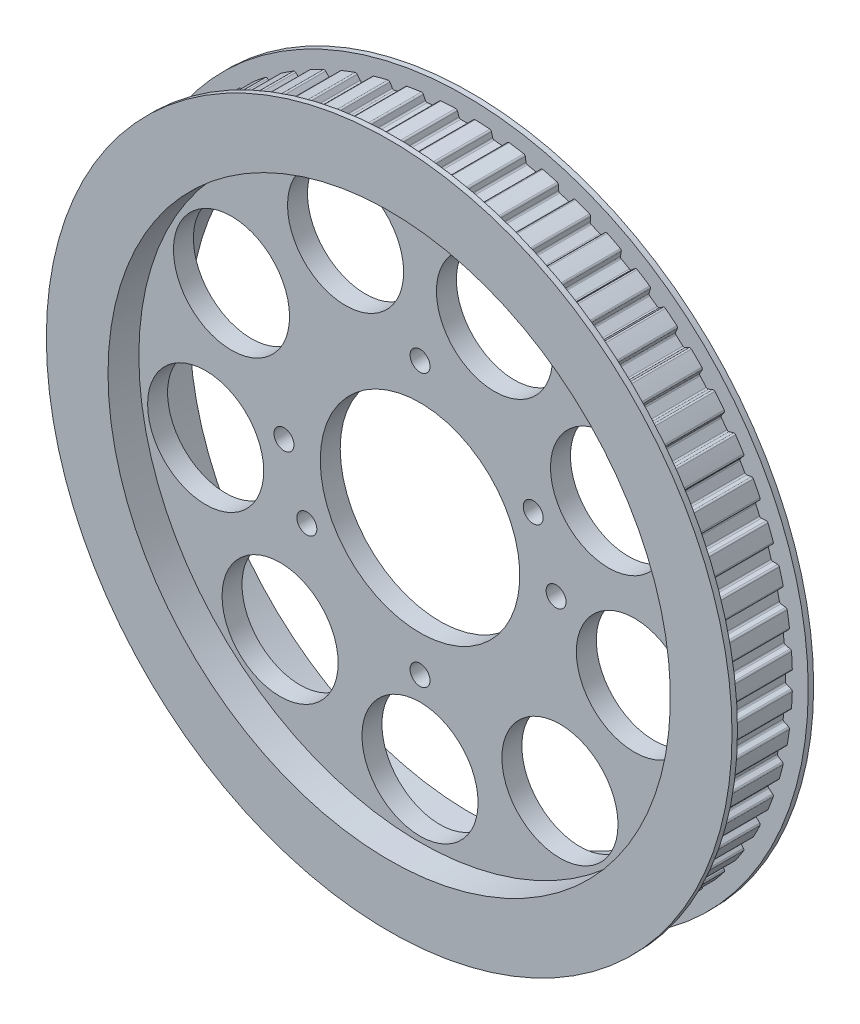
SolidWorks part; units mm, degrees
ref_plane "Front Plane" through (0, 0, 0) normal (0, 0, 1) x (1, 0, 0)
ref_plane "Top Plane" through (0, 0, 0) normal (0, 1, 0) x (1, 0, 0)
ref_plane "Right Plane" through (0, 0, 0) normal (1, 0, 0) x (0, 0, -1)
sketch "Sketch1" plane through (0, 0, 0) normal (0, 1, 0) x (1, 0, 0)
  line L0 (0, 41.5473) -> (0, -30.0211) construction
  line L1 (27.5, 2.75) -> (27.5, -2.75)
  line L2 (27.5, -2.75) -> (77.5, -2.75)
  line L3 (77.5, -2.75) -> (77.5, -11.25)
  line L4 (77.5, -11.25) -> (94.5, -11.25)
  line L5 (94.5, -11.25) -> (94.5, 11.25)
  line L6 (94.5, 11.25) -> (77.5, 11.25)
  line L7 (77.5, 11.25) -> (77.5, 2.75)
  line L8 (77.5, 2.75) -> (27.5, 2.75)
  line L9 (0, 0) -> (27.5, 0) construction
  line L10 (27.5, 0) -> (94.5, 0) construction
  dimension "D1" = 27.5
  dimension "D2" = 17
  dimension "D3" = 22.5
  dimension "D4" = 94.5
  dimension "D5" = 5.5
revolve "Revolve1" add sketch "Sketch1" angle 360 about L0
sketch "Sketch6" plane through (0, 0, 0) normal (0, 0, 1) x (1, 0, 0)
  line L0 (0, 0) -> (0, 89.1601) construction
  line L1 (-2.325, 90.1151) -> (-2.9401, 91.8051) construction
  line L2 (-2.325, 90.1151) -> (-1.6298, 88.2051) construction
  line L3 (-1.6298, 88.2051) -> (1.6298, 88.2051) construction
  line L4 (1.6298, 88.2051) -> (2.325, 90.1151) construction
  line L5 (2.325, 90.1151) -> (-2.325, 90.1151) construction
  line L6 (0, 88.2051) -> (0, 90.1151) construction
  line L7 (-2.9401, 91.8051) -> (2.9401, 91.8051) construction
  line L8 (2.9401, 91.8051) -> (2.325, 90.1151) construction
  line L9 (0, 90.1151) -> (0, 90.1451) construction
  line L10 (0, 90.1451) -> (0, 91.8522) construction
  line L11 (0, 0) -> (9.3198, 88.6717) construction
  line L12 (9.3198, 88.6717) -> (9.4227, 89.6513) construction
  line L13 (9.4227, 89.6513) -> (9.6012, 91.349) construction
  line L14 (0, 90.9986) -> (9.5119, 90.5001) construction
  circle A0 centre (0, 0) radius 94.5
  circle A1 centre (0, 0) radius 89.1601 construction
  circle A2 centre (-1.2727, 88.7151) radius 0.51 construction
  circle A3 centre (1.2727, 88.7151) radius 0.51 construction
  circle A4 centre (0, 0) radius 90.1451
  circle A5 centre (0, 0) radius 94.5 construction
  circle A6 centre (0, 0) radius 91.8522 construction
  dimension "D3" = 40
  dimension "D6" = 1.02
  dimension "D1" = 9.525
  dimension "D2" = 3.6
  dimension "D7" = 6
  dimension "D4" = 1.91
  dimension "D5" = 4.65
extrude "Cut-Extrude6" cut sketch "Sketch6" against normal offset from surface 1.5 and the other way offset from surface 1.5 up to face at (-77.5, 0, -11.25) other way up to face at (-94.5, 0, 11.25)
sketch "Sketch7" plane through (0, 0, 0) normal (0, 0, 1) x (1, 0, 0)
  line L0 (-1.6298, 88.2051) -> (-2.3359, 90.1451)
  line L1 (-2.3359, 90.1451) -> (2.3359, 90.1451)
  line L2 (2.3359, 90.1451) -> (1.6298, 88.2051)
  line L3 (1.6298, 88.2051) -> (-1.6298, 88.2051)
  line L4 (-2.325, 90.1151) -> (-1.6298, 88.2051) construction
  line L5 (1.6298, 88.2051) -> (2.325, 90.1151) construction
  line L6 (7.5991, 87.8923) -> (7.0996, 89.8954)
  line L7 (7.0996, 89.8954) -> (11.7458, 89.4071)
  line L8 (11.7458, 89.4071) -> (10.8408, 87.5515)
  line L9 (10.8408, 87.5515) -> (7.5991, 87.8923)
  line L10 (16.7447, 86.6165) -> (16.4573, 88.6609)
  line L11 (16.4573, 88.6609) -> (21.0271, 87.6895)
  line L12 (21.0271, 87.6895) -> (19.9331, 85.9387)
  line L13 (19.9331, 85.9387) -> (16.7447, 86.6165)
  line L14 (25.7068, 84.3917) -> (25.6348, 86.4549)
  line L15 (25.6348, 86.4549) -> (30.0779, 85.0112)
  line L16 (30.0779, 85.0112) -> (28.8069, 83.3844)
  line L17 (28.8069, 83.3844) -> (25.7068, 84.3917)
  line L18 (34.3873, 81.2423) -> (34.5313, 83.3017)
  line L19 (34.5313, 83.3017) -> (38.7993, 81.4015)
  line L20 (38.7993, 81.4015) -> (37.3652, 79.9165)
  line L21 (37.3652, 79.9165) -> (34.3873, 81.2423)
  line L22 (42.6911, 77.2028) -> (43.0496, 79.2359)
  line L23 (43.0496, 79.2359) -> (47.0955, 76.9)
  line L24 (47.0955, 76.9) -> (45.514, 75.5729)
  line L25 (45.514, 75.5729) -> (42.6911, 77.2028)
  line L26 (50.5271, 72.3174) -> (51.0962, 74.3019)
  line L27 (51.0962, 74.3019) -> (54.8757, 71.5559)
  line L28 (54.8757, 71.5559) -> (53.1642, 70.4014)
  line L29 (53.1642, 70.4014) -> (50.5271, 72.3174)
  line L30 (57.8095, 66.6397) -> (58.5829, 68.5539)
  line L31 (58.5829, 68.5539) -> (62.0548, 65.4278)
  line L32 (62.0548, 65.4278) -> (60.2319, 64.4586)
  line L33 (60.2319, 64.4586) -> (57.8095, 66.6397)
  line L34 (64.4586, 60.2319) -> (65.4278, 62.0548)
  line L35 (65.4278, 62.0548) -> (68.5539, 58.5829)
  line L36 (68.5539, 58.5829) -> (66.6397, 57.8095)
  line L37 (66.6397, 57.8095) -> (64.4586, 60.2319)
  line L38 (70.4014, 53.1642) -> (71.5559, 54.8757)
  line L39 (71.5559, 54.8757) -> (74.3019, 51.0962)
  line L40 (74.3019, 51.0962) -> (72.3174, 50.5271)
  line L41 (72.3174, 50.5271) -> (70.4014, 53.1642)
  line L42 (75.5729, 45.514) -> (76.9, 47.0955)
  line L43 (76.9, 47.0955) -> (79.2359, 43.0496)
  line L44 (79.2359, 43.0496) -> (77.2028, 42.6911)
  line L45 (77.2028, 42.6911) -> (75.5729, 45.514)
  line L46 (79.9165, 37.3652) -> (81.4015, 38.7993)
  line L47 (81.4015, 38.7993) -> (83.3017, 34.5313)
  line L48 (83.3017, 34.5313) -> (81.2423, 34.3873)
  line L49 (81.2423, 34.3873) -> (79.9165, 37.3652)
  line L50 (83.3844, 28.8069) -> (85.0112, 30.0779)
  line L51 (85.0112, 30.0779) -> (86.4549, 25.6348)
  line L52 (86.4549, 25.6348) -> (84.3917, 25.7068)
  line L53 (84.3917, 25.7068) -> (83.3844, 28.8069)
  line L54 (85.9387, 19.9331) -> (87.6895, 21.0271)
  line L55 (87.6895, 21.0271) -> (88.6609, 16.4573)
  line L56 (88.6609, 16.4573) -> (86.6165, 16.7447)
  line L57 (86.6165, 16.7447) -> (85.9387, 19.9331)
  line L58 (87.5515, 10.8408) -> (89.4071, 11.7458)
  line L59 (89.4071, 11.7458) -> (89.8954, 7.0996)
  line L60 (89.8954, 7.0996) -> (87.8923, 7.5991)
  line L61 (87.8923, 7.5991) -> (87.5515, 10.8408)
  line L62 (88.2051, 1.6298) -> (90.1451, 2.3359)
  line L63 (90.1451, 2.3359) -> (90.1451, -2.3359)
  line L64 (90.1451, -2.3359) -> (88.2051, -1.6298)
  line L65 (88.2051, -1.6298) -> (88.2051, 1.6298)
  line L66 (87.8923, -7.5991) -> (89.8954, -7.0996)
  line L67 (89.8954, -7.0996) -> (89.4071, -11.7458)
  line L68 (89.4071, -11.7458) -> (87.5515, -10.8408)
  line L69 (87.5515, -10.8408) -> (87.8923, -7.5991)
  line L70 (86.6165, -16.7447) -> (88.6609, -16.4573)
  line L71 (88.6609, -16.4573) -> (87.6895, -21.0271)
  line L72 (87.6895, -21.0271) -> (85.9387, -19.9331)
  line L73 (85.9387, -19.9331) -> (86.6165, -16.7447)
  line L74 (84.3917, -25.7068) -> (86.4549, -25.6348)
  line L75 (86.4549, -25.6348) -> (85.0112, -30.0779)
  line L76 (85.0112, -30.0779) -> (83.3844, -28.8069)
  line L77 (83.3844, -28.8069) -> (84.3917, -25.7068)
  line L78 (81.2423, -34.3873) -> (83.3017, -34.5313)
  line L79 (83.3017, -34.5313) -> (81.4015, -38.7993)
  line L80 (81.4015, -38.7993) -> (79.9165, -37.3652)
  line L81 (79.9165, -37.3652) -> (81.2423, -34.3873)
  line L82 (77.2028, -42.6911) -> (79.2359, -43.0496)
  line L83 (79.2359, -43.0496) -> (76.9, -47.0955)
  line L84 (76.9, -47.0955) -> (75.5729, -45.514)
  line L85 (75.5729, -45.514) -> (77.2028, -42.6911)
  line L86 (72.3174, -50.5271) -> (74.3019, -51.0962)
  line L87 (74.3019, -51.0962) -> (71.5559, -54.8757)
  line L88 (71.5559, -54.8757) -> (70.4014, -53.1642)
  line L89 (70.4014, -53.1642) -> (72.3174, -50.5271)
  line L90 (66.6397, -57.8095) -> (68.5539, -58.5829)
  line L91 (68.5539, -58.5829) -> (65.4278, -62.0548)
  line L92 (65.4278, -62.0548) -> (64.4586, -60.2319)
  line L93 (64.4586, -60.2319) -> (66.6397, -57.8095)
  line L94 (60.2319, -64.4586) -> (62.0548, -65.4278)
  line L95 (62.0548, -65.4278) -> (58.5829, -68.5539)
  line L96 (58.5829, -68.5539) -> (57.8095, -66.6397)
  line L97 (57.8095, -66.6397) -> (60.2319, -64.4586)
  line L98 (53.1642, -70.4014) -> (54.8757, -71.5559)
  line L99 (54.8757, -71.5559) -> (51.0962, -74.3019)
  line L100 (51.0962, -74.3019) -> (50.5271, -72.3174)
  line L101 (50.5271, -72.3174) -> (53.1642, -70.4014)
  line L102 (45.514, -75.5729) -> (47.0955, -76.9)
  line L103 (47.0955, -76.9) -> (43.0496, -79.2359)
  line L104 (43.0496, -79.2359) -> (42.6911, -77.2028)
  line L105 (42.6911, -77.2028) -> (45.514, -75.5729)
  line L106 (37.3652, -79.9165) -> (38.7993, -81.4015)
  line L107 (38.7993, -81.4015) -> (34.5313, -83.3017)
  line L108 (34.5313, -83.3017) -> (34.3873, -81.2423)
  line L109 (34.3873, -81.2423) -> (37.3652, -79.9165)
  line L110 (28.8069, -83.3844) -> (30.0779, -85.0112)
  line L111 (30.0779, -85.0112) -> (25.6348, -86.4549)
  line L112 (25.6348, -86.4549) -> (25.7068, -84.3917)
  line L113 (25.7068, -84.3917) -> (28.8069, -83.3844)
  line L114 (19.9331, -85.9387) -> (21.0271, -87.6895)
  line L115 (21.0271, -87.6895) -> (16.4573, -88.6609)
  line L116 (16.4573, -88.6609) -> (16.7447, -86.6165)
  line L117 (16.7447, -86.6165) -> (19.9331, -85.9387)
  line L118 (10.8408, -87.5515) -> (11.7458, -89.4071)
  line L119 (11.7458, -89.4071) -> (7.0996, -89.8954)
  line L120 (7.0996, -89.8954) -> (7.5991, -87.8923)
  line L121 (7.5991, -87.8923) -> (10.8408, -87.5515)
  line L122 (1.6298, -88.2051) -> (2.3359, -90.1451)
  line L123 (2.3359, -90.1451) -> (-2.3359, -90.1451)
  line L124 (-2.3359, -90.1451) -> (-1.6298, -88.2051)
  line L125 (-1.6298, -88.2051) -> (1.6298, -88.2051)
  line L126 (-7.5991, -87.8923) -> (-7.0996, -89.8954)
  line L127 (-7.0996, -89.8954) -> (-11.7458, -89.4071)
  line L128 (-11.7458, -89.4071) -> (-10.8408, -87.5515)
  line L129 (-10.8408, -87.5515) -> (-7.5991, -87.8923)
  line L130 (-16.7447, -86.6165) -> (-16.4573, -88.6609)
  line L131 (-16.4573, -88.6609) -> (-21.0271, -87.6895)
  line L132 (-21.0271, -87.6895) -> (-19.9331, -85.9387)
  line L133 (-19.9331, -85.9387) -> (-16.7447, -86.6165)
  line L134 (-25.7068, -84.3917) -> (-25.6348, -86.4549)
  line L135 (-25.6348, -86.4549) -> (-30.0779, -85.0112)
  line L136 (-30.0779, -85.0112) -> (-28.8069, -83.3844)
  line L137 (-28.8069, -83.3844) -> (-25.7068, -84.3917)
  line L138 (-34.3873, -81.2423) -> (-34.5313, -83.3017)
  line L139 (-34.5313, -83.3017) -> (-38.7993, -81.4015)
  line L140 (-38.7993, -81.4015) -> (-37.3652, -79.9165)
  line L141 (-37.3652, -79.9165) -> (-34.3873, -81.2423)
  line L142 (-42.6911, -77.2028) -> (-43.0496, -79.2359)
  line L143 (-43.0496, -79.2359) -> (-47.0955, -76.9)
  line L144 (-47.0955, -76.9) -> (-45.514, -75.5729)
  line L145 (-45.514, -75.5729) -> (-42.6911, -77.2028)
  line L146 (-50.5271, -72.3174) -> (-51.0962, -74.3019)
  line L147 (-51.0962, -74.3019) -> (-54.8757, -71.5559)
  line L148 (-54.8757, -71.5559) -> (-53.1642, -70.4014)
  line L149 (-53.1642, -70.4014) -> (-50.5271, -72.3174)
  line L150 (-57.8095, -66.6397) -> (-58.5829, -68.5539)
  line L151 (-58.5829, -68.5539) -> (-62.0548, -65.4278)
  line L152 (-62.0548, -65.4278) -> (-60.2319, -64.4586)
  line L153 (-60.2319, -64.4586) -> (-57.8095, -66.6397)
  line L154 (-64.4586, -60.2319) -> (-65.4278, -62.0548)
  line L155 (-65.4278, -62.0548) -> (-68.5539, -58.5829)
  line L156 (-68.5539, -58.5829) -> (-66.6397, -57.8095)
  line L157 (-66.6397, -57.8095) -> (-64.4586, -60.2319)
  line L158 (-70.4014, -53.1642) -> (-71.5559, -54.8757)
  line L159 (-71.5559, -54.8757) -> (-74.3019, -51.0962)
  line L160 (-74.3019, -51.0962) -> (-72.3174, -50.5271)
  line L161 (-72.3174, -50.5271) -> (-70.4014, -53.1642)
  line L162 (-75.5729, -45.514) -> (-76.9, -47.0955)
  line L163 (-76.9, -47.0955) -> (-79.2359, -43.0496)
  line L164 (-79.2359, -43.0496) -> (-77.2028, -42.6911)
  line L165 (-77.2028, -42.6911) -> (-75.5729, -45.514)
  line L166 (-79.9165, -37.3652) -> (-81.4015, -38.7993)
  line L167 (-81.4015, -38.7993) -> (-83.3017, -34.5313)
  line L168 (-83.3017, -34.5313) -> (-81.2423, -34.3873)
  line L169 (-81.2423, -34.3873) -> (-79.9165, -37.3652)
  line L170 (-83.3844, -28.8069) -> (-85.0112, -30.0779)
  line L171 (-85.0112, -30.0779) -> (-86.4549, -25.6348)
  line L172 (-86.4549, -25.6348) -> (-84.3917, -25.7068)
  line L173 (-84.3917, -25.7068) -> (-83.3844, -28.8069)
  line L174 (-85.9387, -19.9331) -> (-87.6895, -21.0271)
  line L175 (-87.6895, -21.0271) -> (-88.6609, -16.4573)
  line L176 (-88.6609, -16.4573) -> (-86.6165, -16.7447)
  line L177 (-86.6165, -16.7447) -> (-85.9387, -19.9331)
  line L178 (-87.5515, -10.8408) -> (-89.4071, -11.7458)
  line L179 (-89.4071, -11.7458) -> (-89.8954, -7.0996)
  line L180 (-89.8954, -7.0996) -> (-87.8923, -7.5991)
  line L181 (-87.8923, -7.5991) -> (-87.5515, -10.8408)
  line L182 (-88.2051, -1.6298) -> (-90.1451, -2.3359)
  line L183 (-90.1451, -2.3359) -> (-90.1451, 2.3359)
  line L184 (-90.1451, 2.3359) -> (-88.2051, 1.6298)
  line L185 (-88.2051, 1.6298) -> (-88.2051, -1.6298)
  line L186 (-87.8923, 7.5991) -> (-89.8954, 7.0996)
  line L187 (-89.8954, 7.0996) -> (-89.4071, 11.7458)
  line L188 (-89.4071, 11.7458) -> (-87.5515, 10.8408)
  line L189 (-87.5515, 10.8408) -> (-87.8923, 7.5991)
  line L190 (-86.6165, 16.7447) -> (-88.6609, 16.4573)
  line L191 (-88.6609, 16.4573) -> (-87.6895, 21.0271)
  line L192 (-87.6895, 21.0271) -> (-85.9387, 19.9331)
  line L193 (-85.9387, 19.9331) -> (-86.6165, 16.7447)
  line L194 (-84.3917, 25.7068) -> (-86.4549, 25.6348)
  line L195 (-86.4549, 25.6348) -> (-85.0112, 30.0779)
  line L196 (-85.0112, 30.0779) -> (-83.3844, 28.8069)
  line L197 (-83.3844, 28.8069) -> (-84.3917, 25.7068)
  line L198 (-81.2423, 34.3873) -> (-83.3017, 34.5313)
  line L199 (-83.3017, 34.5313) -> (-81.4015, 38.7993)
  line L200 (-81.4015, 38.7993) -> (-79.9165, 37.3652)
  line L201 (-79.9165, 37.3652) -> (-81.2423, 34.3873)
  line L202 (-77.2028, 42.6911) -> (-79.2359, 43.0496)
  line L203 (-79.2359, 43.0496) -> (-76.9, 47.0955)
  line L204 (-76.9, 47.0955) -> (-75.5729, 45.514)
  line L205 (-75.5729, 45.514) -> (-77.2028, 42.6911)
  line L206 (-72.3174, 50.5271) -> (-74.3019, 51.0962)
  line L207 (-74.3019, 51.0962) -> (-71.5559, 54.8757)
  line L208 (-71.5559, 54.8757) -> (-70.4014, 53.1642)
  line L209 (-70.4014, 53.1642) -> (-72.3174, 50.5271)
  line L210 (-66.6397, 57.8095) -> (-68.5539, 58.5829)
  line L211 (-68.5539, 58.5829) -> (-65.4278, 62.0548)
  line L212 (-65.4278, 62.0548) -> (-64.4586, 60.2319)
  line L213 (-64.4586, 60.2319) -> (-66.6397, 57.8095)
  line L214 (-60.2319, 64.4586) -> (-62.0548, 65.4278)
  line L215 (-62.0548, 65.4278) -> (-58.5829, 68.5539)
  line L216 (-58.5829, 68.5539) -> (-57.8095, 66.6397)
  line L217 (-57.8095, 66.6397) -> (-60.2319, 64.4586)
  line L218 (-53.1642, 70.4014) -> (-54.8757, 71.5559)
  line L219 (-54.8757, 71.5559) -> (-51.0962, 74.3019)
  line L220 (-51.0962, 74.3019) -> (-50.5271, 72.3174)
  line L221 (-50.5271, 72.3174) -> (-53.1642, 70.4014)
  line L222 (-45.514, 75.5729) -> (-47.0955, 76.9)
  line L223 (-47.0955, 76.9) -> (-43.0496, 79.2359)
  line L224 (-43.0496, 79.2359) -> (-42.6911, 77.2028)
  line L225 (-42.6911, 77.2028) -> (-45.514, 75.5729)
  line L226 (-37.3652, 79.9165) -> (-38.7993, 81.4015)
  line L227 (-38.7993, 81.4015) -> (-34.5313, 83.3017)
  line L228 (-34.5313, 83.3017) -> (-34.3873, 81.2423)
  line L229 (-34.3873, 81.2423) -> (-37.3652, 79.9165)
  line L230 (-28.8069, 83.3844) -> (-30.0779, 85.0112)
  line L231 (-30.0779, 85.0112) -> (-25.6348, 86.4549)
  line L232 (-25.6348, 86.4549) -> (-25.7068, 84.3917)
  line L233 (-25.7068, 84.3917) -> (-28.8069, 83.3844)
  line L234 (-19.9331, 85.9387) -> (-21.0271, 87.6895)
  line L235 (-21.0271, 87.6895) -> (-16.4573, 88.6609)
  line L236 (-16.4573, 88.6609) -> (-16.7447, 86.6165)
  line L237 (-16.7447, 86.6165) -> (-19.9331, 85.9387)
  line L238 (-10.8408, 87.5515) -> (-11.7458, 89.4071)
  line L239 (-11.7458, 89.4071) -> (-7.0996, 89.8954)
  line L240 (-7.0996, 89.8954) -> (-7.5991, 87.8923)
  line L241 (-7.5991, 87.8923) -> (-10.8408, 87.5515)
  circle A0 centre (0, 0) radius 90.1451 construction
  point P251 (0, 0)
  dimension "D1" = 60
extrude "Cut-Extrude7" cut sketch "Sketch7" against normal up to surface (9.75 mm away) and the other way up to surface (9.75 mm away) up to face at (94.5, 0, -9.75) other way up to face at (-90.1451, 0, 9.75)
fillet "Fillet1" radius 0.51 240 edges at (88.2051, -1.6298, 0) (88.2051, 1.6298, 0) (90.1151, 2.325, 0) (89.8645, 7.1073, 0) (87.8923, 7.5991, 0) (87.5515, 10.8408, 0) (89.3784, 11.7319, 0) (88.6293, 16.4618, 0) (86.6165, 16.7447, 0) (85.9387, 19.9331, 0) (87.6625, 21.0102, 0) (86.423, 25.6359, 0) (84.3917, 25.7068, 0) (83.3844, 28.8069, 0) (84.9861, 30.0583, 0) (83.2699, 34.5291, 0) (81.2423, 34.3873, 0) (79.9165, 37.3652, 0) (81.3786, 38.7771, 0) (79.2045, 43.044, 0) (77.2028, 42.6911, 0) (75.5729, 45.514, 0) (76.8795, 47.0711, 0) (74.2712, 51.0874, 0) (72.3174, 50.5271, 0) (70.4014, 53.1642, 0) (71.538, 54.8493, 0) (68.5243, 58.571, 0) (66.6397, 57.8095, 0) (64.4586, 60.2319, 0) (65.4128, 62.0266, 0) (62.0266, 65.4128, 0) (60.2319, 64.4586, 0) (57.8095, 66.6397, 0) (58.571, 68.5243, 0) (54.8493, 71.538, 0) (53.1642, 70.4014, 0) (50.5271, 72.3174, 0) (51.0874, 74.2712, 0) (47.0711, 76.8795, 0) (45.514, 75.5729, 0) (42.6911, 77.2028, 0) (43.044, 79.2045, 0) (38.7771, 81.3786, 0) (37.3652, 79.9165, 0) (34.3873, 81.2423, 0) (34.5291, 83.2699, 0) (30.0583, 84.9861, 0) (28.8069, 83.3844, 0) (25.7068, 84.3917, 0) (25.6359, 86.423, 0) (21.0102, 87.6625, 0) (19.9331, 85.9387, 0) (16.7447, 86.6165, 0) (16.4618, 88.6293, 0) (11.7319, 89.3784, 0) (10.8408, 87.5515, 0) (7.5991, 87.8923, 0) (7.1073, 89.8645, 0) (2.325, 90.1151, 0) (1.6298, 88.2051, 0) (-1.6298, 88.2051, 0) (-7.1073, 89.8645, 0) (-7.5991, 87.8923, 0) (-10.8408, 87.5515, 0) (-11.7319, 89.3784, 0) (-16.4618, 88.6293, 0) (-16.7447, 86.6165, 0) (-19.9331, 85.9387, 0) (-21.0102, 87.6625, 0) (-25.6359, 86.423, 0) (-25.7068, 84.3917, 0) (-28.8069, 83.3844, 0) (-30.0583, 84.9861, 0) (-34.5291, 83.2699, 0) (-34.3873, 81.2423, 0) (-37.3652, 79.9165, 0) (-38.7771, 81.3786, 0) (-43.044, 79.2045, 0) (-42.6911, 77.2028, 0) (-45.514, 75.5729, 0) (-47.0711, 76.8795, 0) (-51.0874, 74.2712, 0) (-50.5271, 72.3174, 0) (-53.1642, 70.4014, 0) (-54.8493, 71.538, 0) (-58.571, 68.5243, 0) (-57.8095, 66.6397, 0) (-60.2319, 64.4586, 0) (-62.0266, 65.4128, 0) (-65.4128, 62.0266, 0) (-64.4586, 60.2319, 0) (-66.6397, 57.8095, 0) (-68.5243, 58.571, 0) (-71.538, 54.8493, 0) (-70.4014, 53.1642, 0) (-72.3174, 50.5271, 0) (-74.2712, 51.0874, 0) (-76.8795, 47.0711, 0) (-75.5729, 45.514, 0) (-77.2028, 42.6911, 0) (-79.2045, 43.044, 0) (-81.3786, 38.7771, 0) (-79.9165, 37.3652, 0) (-81.2423, 34.3873, 0) (-83.2699, 34.5291, 0) (-84.9861, 30.0583, 0) (-83.3844, 28.8069, 0) (-84.3917, 25.7068, 0) (-86.423, 25.6359, 0) (-87.6625, 21.0102, 0) (-85.9387, 19.9331, 0) (-86.6165, 16.7447, 0) (-88.6293, 16.4618, 0) (-89.3784, 11.7319, 0) (-87.5515, 10.8408, 0) (-87.8923, 7.5991, 0) (-89.8645, 7.1073, 0) (-90.1151, 2.325, 0) (-88.2051, 1.6298, 0) (-88.2051, -1.6298, 0) (-90.1151, -2.325, 0) (-89.8645, -7.1073, 0) (-87.8923, -7.5991, 0) (-87.5515, -10.8408, 0) (-89.3784, -11.7319, 0) (-88.6293, -16.4618, 0) (-86.6165, -16.7447, 0) (-85.9387, -19.9331, 0) (-87.6625, -21.0102, 0) (-86.423, -25.6359, 0) (-84.3917, -25.7068, 0) (-83.3844, -28.8069, 0) (-84.9861, -30.0583, 0) (-83.2699, -34.5291, 0) (-81.2423, -34.3873, 0) (-79.9165, -37.3652, 0) (-81.3786, -38.7771, 0) (-79.2045, -43.044, 0) (-77.2028, -42.6911, 0) (-75.5729, -45.514, 0) (-76.8795, -47.0711, 0) (-74.2712, -51.0874, 0) (-72.3174, -50.5271, 0) (-70.4014, -53.1642, 0) (-71.538, -54.8493, 0) (-68.5243, -58.571, 0) (-66.6397, -57.8095, 0) (-64.4586, -60.2319, 0) (-65.4128, -62.0266, 0) (-62.0266, -65.4128, 0) (-60.2319, -64.4586, 0) (-57.8095, -66.6397, 0) (-58.571, -68.5243, 0) (-54.8493, -71.538, 0) (-53.1642, -70.4014, 0) (-50.5271, -72.3174, 0) (-51.0874, -74.2712, 0) (-47.0711, -76.8795, 0) (-45.514, -75.5729, 0) (-42.6911, -77.2028, 0) (-43.044, -79.2045, 0) (-38.7771, -81.3786, 0) (-37.3652, -79.9165, 0) (-34.3873, -81.2423, 0) (-34.5291, -83.2699, 0) (-30.0583, -84.9861, 0) (-28.8069, -83.3844, 0) (-25.7068, -84.3917, 0) (-25.6359, -86.423, 0) (-21.0102, -87.6625, 0) (-19.9331, -85.9387, 0) (-16.7447, -86.6165, 0) (-16.4618, -88.6293, 0) (-11.7319, -89.3784, 0) (-10.8408, -87.5515, 0) (-7.5991, -87.8923, 0) (-7.1073, -89.8645, 0) (-2.325, -90.1151, 0) (-1.6298, -88.2051, 0) (1.6298, -88.2051, 0) (2.325, -90.1151, 0) (7.1073, -89.8645, 0) (7.5991, -87.8923, 0) (10.8408, -87.5515, 0) (11.7319, -89.3784, 0) (16.4618, -88.6293, 0) (16.7447, -86.6165, 0) (19.9331, -85.9387, 0) (21.0102, -87.6625, 0) (25.6359, -86.423, 0) (25.7068, -84.3917, 0) (28.8069, -83.3844, 0) (30.0583, -84.9861, 0) (34.5291, -83.2699, 0) (34.3873, -81.2423, 0) (37.3652, -79.9165, 0) (38.7771, -81.3786, 0) (43.044, -79.2045, 0) (42.6911, -77.2028, 0) (45.514, -75.5729, 0) (47.0711, -76.8795, 0) (51.0874, -74.2712, 0) (50.5271, -72.3174, 0) (53.1642, -70.4014, 0) (54.8493, -71.538, 0) (58.571, -68.5243, 0) (57.8095, -66.6397, 0) (60.2319, -64.4586, 0) (62.0266, -65.4128, 0) (65.4128, -62.0266, 0) (64.4586, -60.2319, 0) (66.6397, -57.8095, 0) (68.5243, -58.571, 0) (71.538, -54.8493, 0) (70.4014, -53.1642, 0) (72.3174, -50.5271, 0) (74.2712, -51.0874, 0) (76.8795, -47.0711, 0) (75.5729, -45.514, 0) (77.2028, -42.6911, 0) (79.2045, -43.044, 0) (81.3786, -38.7771, 0) (79.9165, -37.3652, 0) (81.2423, -34.3873, 0) (83.2699, -34.5291, 0) (84.9861, -30.0583, 0) (83.3844, -28.8069, 0) (84.3917, -25.7068, 0) (86.423, -25.6359, 0) (87.6625, -21.0102, 0) (85.9387, -19.9331, 0) (86.6165, -16.7447, 0) (88.6293, -16.4618, 0) (89.3784, -11.7319, 0) (87.5515, -10.8408, 0) (87.8923, -7.5991, 0) (89.8645, -7.1073, 0) (90.1151, -2.325, 0) (-2.325, 90.1151, 0)
sketch "Sketch3" plane through (0, 0, 0) normal (0, 0, 1) x (1, 0, 0)
  line L0 (0, 0) -> (0, 77.5) construction
  line L1 (0, 0) -> (9.4056, 25.8415) construction
  line L2 (15.0489, 41.3465) -> (20.5212, 56.3816) construction
  line L3 (20.5212, 56.3816) -> (25.9935, 71.4166) construction
  line L4 (25.9935, 71.4166) -> (26.5066, 72.8262) construction
  line L5 (9.4056, 25.8415) -> (15.0489, 41.3465) construction
  line L6 (-20.5212, 56.3816) -> (20.5212, 56.3816) construction
  circle A0 centre (20.5212, 56.3816) radius 16
  circle A1 centre (0, 0) radius 77.5 construction
  circle A2 centre (0, 0) radius 27.5 construction
  circle A3 centre (51.9615, 30) radius 16
  circle A4 centre (59.0885, -10.4189) radius 16
  circle A5 centre (38.5673, -45.9627) radius 16
  circle A6 centre (0, -60) radius 16
  circle A7 centre (-38.5673, -45.9627) radius 16
  circle A8 centre (-59.0885, -10.4189) radius 16
  circle A9 centre (-51.9615, 30) radius 16
  circle A10 centre (-20.5212, 56.3816) radius 16
  point P33 (0, 0)
  dimension "D2" = 32
  dimension "D1" = 16.5
  dimension "D3" = 9
extrude "Cut-Extrude3" cut sketch "Sketch3" against normal through all both and the other way through all
sketch "Sketch4" plane through (0, 0, 0) normal (0, 0, 1) x (1, 0, 0)
  line L0 (0, 0) -> (0, 27.5) construction
  line L1 (0, 27.5) -> (0, 34.75) construction
  line L2 (0, 34.75) -> (0, 37.5) construction
  line L3 (0, 37.5) -> (0, 40.25) construction
  line L4 (0, 40.25) -> (0, 77.5) construction
  circle A0 centre (0, 37.5) radius 2.75
  circle A1 centre (0, 0) radius 27.5 construction
  circle A2 centre (0, 0) radius 77.5 construction
  circle A3 centre (37.5, 0) radius 2.75
  circle A4 centre (0, -37.5) radius 2.75
  circle A5 centre (-37.5, 0) radius 2.75
  point P22 (0, 0)
  dimension "D1" = 5.5
  dimension "D2" = 7.25
  dimension "D3" = 4
extrude "Cut-Extrude4" cut sketch "Sketch4" against normal through all both and the other way through all
sketch "Sketch5" plane through (0, 0, 0) normal (0, 0, 1) x (1, 0, 0)
  line L0 (-31.198, -16.9391) -> (-28.7813, -15.6269) construction
  line L1 (-28.7813, -15.6269) -> (-24.1675, -13.1219) construction
  line L2 (-24.1675, -13.1219) -> (0, 0) construction
  line L3 (0, 0) -> (24.1675, 13.1219) construction
  line L4 (24.1675, 13.1219) -> (28.7813, 15.6269) construction
  line L5 (28.7813, 15.6269) -> (31.198, 16.9391) construction
  line L6 (0, 0) -> (0, 77.5) construction
  circle A0 centre (31.198, 16.9391) radius 2.75
  circle A1 centre (-31.198, -16.9391) radius 2.75
  circle A2 centre (0, 0) radius 27.5 construction
  circle A4 centre (0, 0) radius 77.5 construction
  dimension "D1" = 5.5
  dimension "D2" = 5.25
  dimension "D3" = 61.5
extrude "Cut-Extrude5" cut sketch "Sketch5" against normal through all both and the other way through all
